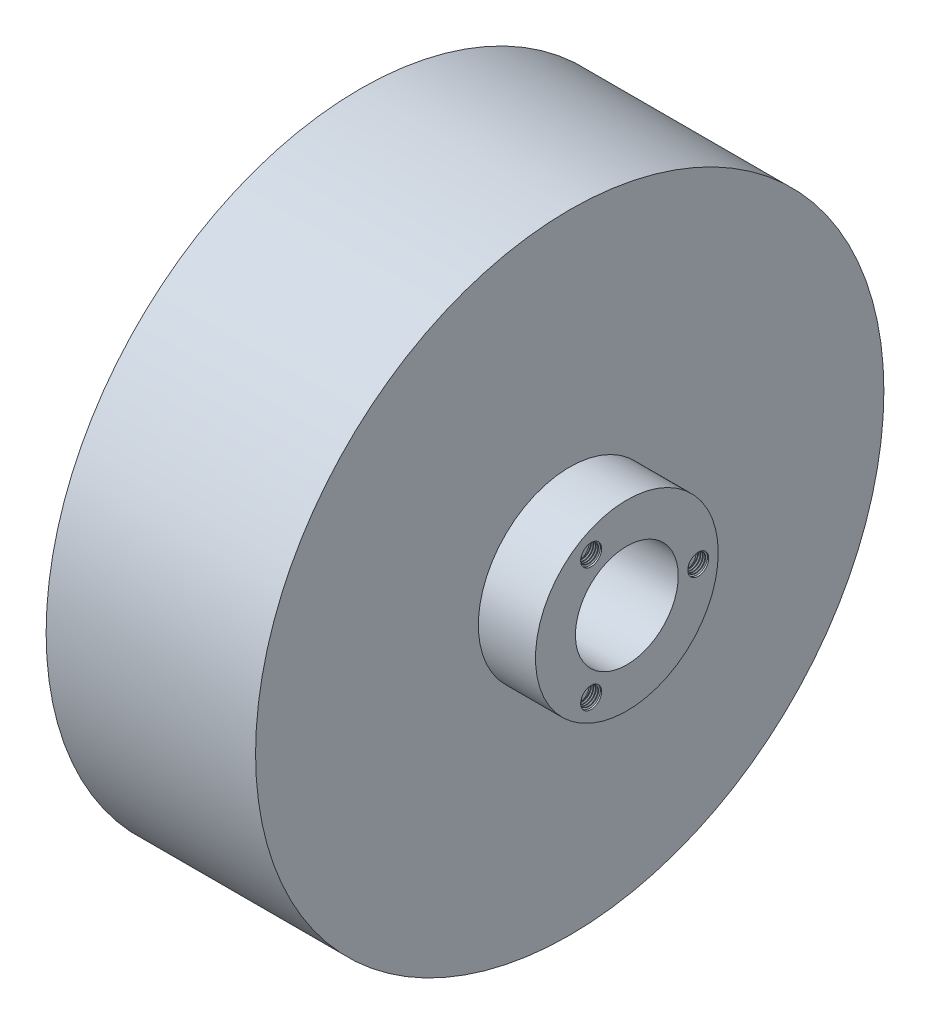
SolidWorks part; units mm, degrees
ref_plane "Front Plane" through (0, 0, 0) normal (0, 0, 1) x (1, 0, 0)
ref_plane "Top Plane" through (0, 0, 0) normal (0, 1, 0) x (1, 0, 0)
ref_plane "Right Plane" through (0, 0, 0) normal (1, 0, 0) x (0, 0, -1)
sketch "Sketch1" plane through (0, 0, 0) normal (1, 0, 0) x (0, 0, -1)
  circle A0 centre (0, 0) radius 165
extrude "Boss-Extrude1" add sketch "Sketch1" along normal blind 110 contours A0
sketch "Sketch2" plane through (110, 0, 0) normal (1, 0, 0) x (0, 0, -1)
  circle A0 centre (0, 0) radius 48
extrude "Boss-Extrude2" add sketch "Sketch2" along normal blind 30 contours A0
sketch "Sketch3" plane through (140, 0, 0) normal (1, 0, 0) x (0, 0, -1)
  circle A0 centre (0, 0) radius 27
extrude "Cut-Extrude1" cut sketch "Sketch3" against normal blind 40 contours A0
sketch "Sketch12" plane through (140, 0, 0) normal (1, 0, 0) x (0, 0, -1)
  circle A2 centre (37.5, 0) radius 5.5
extrude "Cut-Extrude2" cut sketch "Sketch12" against normal blind 6 contours A2
pattern_circular "CirPattern1" count 3 over 360 about axis through (0, 0, 0) along (1, 0, 0) of "Cut-Extrude2"
thread "Thread1" pitch 1.25 method extrude profile "Thread Profile2" start angle 0, offset 0, length 0, pitch 1.25, diameter 11
ref_plane "Plane2" through (140, 0, -32) normal (0, -1, 0) x (0, 0, 1)
sketch "Thread Profile2" plane through (140, 0, -32) normal (0, -1, 0) x (0, 0, 1)
  line L0 (0, 0) -> (0, 1.25) construction
  line L11 (0, 0) -> (0, 1.0937)
  line L12 (0, 1.0937) -> (-0.6766, 0.7031)
  line L13 (-0.6766, 0.7031) -> (-0.6766, 0.3906)
  line L15 (-0.6766, 0.3906) -> (0, 0)
  line L17 (-0.6766, 0.5469) -> (0, 0.5469) construction
  point P2 (0, 0)
  dimension "Pitch" = 1.25
  dimension "Profile_Angle" = 60
  dimension "Profile_Land" = 0.3125
  dimension "Profile_Height" = 0.6766
thread "Thread2" pitch 1.25 method extrude profile "Thread Profile3" start angle 0, offset 0, length 0, pitch 1.25, diameter 11
ref_plane "Plane3" through (140, 32.476, 24.25) normal (0, -1, 0) x (0, 0, 1)
sketch "Thread Profile3" plane through (140, 32.476, 24.25) normal (0, -1, 0) x (0, 0, 1)
  line L0 (0, 0) -> (0, 1.25) construction
  line L11 (0, 0) -> (0, 1.0937)
  line L12 (0, 1.0937) -> (-0.6766, 0.7031)
  line L13 (-0.6766, 0.7031) -> (-0.6766, 0.3906)
  line L15 (-0.6766, 0.3906) -> (0, 0)
  line L17 (-0.6766, 0.5469) -> (0, 0.5469) construction
  point P2 (0, 0)
  dimension "Pitch" = 1.25
  dimension "Profile_Angle" = 60
  dimension "Profile_Land" = 0.3125
  dimension "Profile_Height" = 0.6766
thread "Thread3" pitch 1.25 method extrude profile "Thread Profile4" start angle 0, offset 0, length 0, pitch 1.25, diameter 11
ref_plane "Plane4" through (140, -32.476, 24.25) normal (0, -1, 0) x (0, 0, 1)
sketch "Thread Profile4" plane through (140, -32.476, 24.25) normal (0, -1, 0) x (0, 0, 1)
  line L0 (0, 0) -> (0, 1.25) construction
  line L11 (0, 0) -> (0, 1.0937)
  line L12 (0, 1.0937) -> (-0.6766, 0.7031)
  line L13 (-0.6766, 0.7031) -> (-0.6766, 0.3906)
  line L15 (-0.6766, 0.3906) -> (0, 0)
  line L17 (-0.6766, 0.5469) -> (0, 0.5469) construction
  point P2 (0, 0)
  dimension "Pitch" = 1.25
  dimension "Profile_Angle" = 60
  dimension "Profile_Land" = 0.3125
  dimension "Profile_Height" = 0.6766
